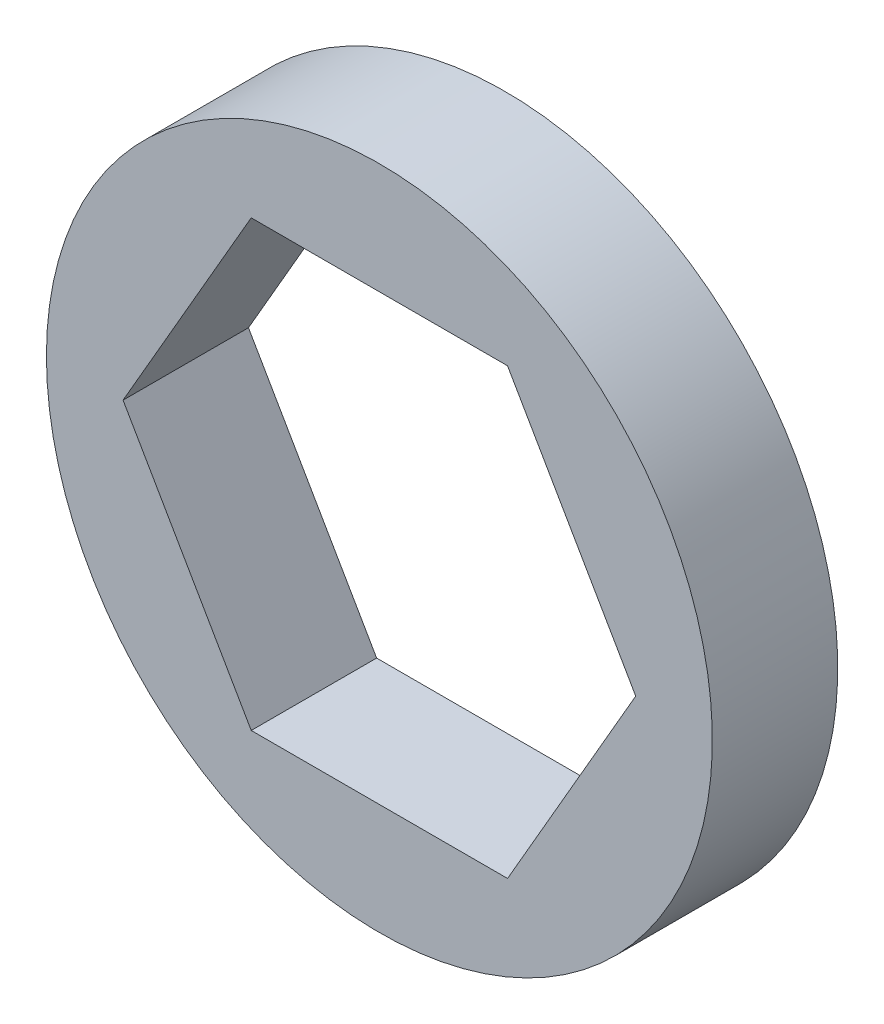
SolidWorks part; units mm, degrees
ref_plane "Front Plane" through (0, 0, 0) normal (0, 0, 1) x (1, 0, 0)
ref_plane "Top Plane" through (0, 0, 0) normal (0, 1, 0) x (1, 0, 0)
ref_plane "Right Plane" through (0, 0, 0) normal (1, 0, 0) x (0, 0, -1)
sketch "Sketch1" plane through (0, 0, 0) normal (0, 0, 1) x (1, 0, 0)
  line L1 (3.6662, 6.35) -> (-3.6662, 6.35)
  line L2 (-3.6662, 6.35) -> (-7.3323, 0)
  line L3 (-7.3323, 0) -> (-3.6662, -6.35)
  line L4 (-3.6662, -6.35) -> (3.6662, -6.35)
  line L5 (3.6662, -6.35) -> (7.3323, 0)
  line L6 (7.3323, 0) -> (3.6662, 6.35)
  circle A1 centre (0, 0) radius 9.525
  circle A2 centre (0, 0) radius 6.35 construction
  point P1 (0, 0)
  dimension "D1" = 19.05
  dimension ".5" = 12.7
extrude "Boss-Extrude1" add sketch "Sketch1" along normal blind 3.5875
